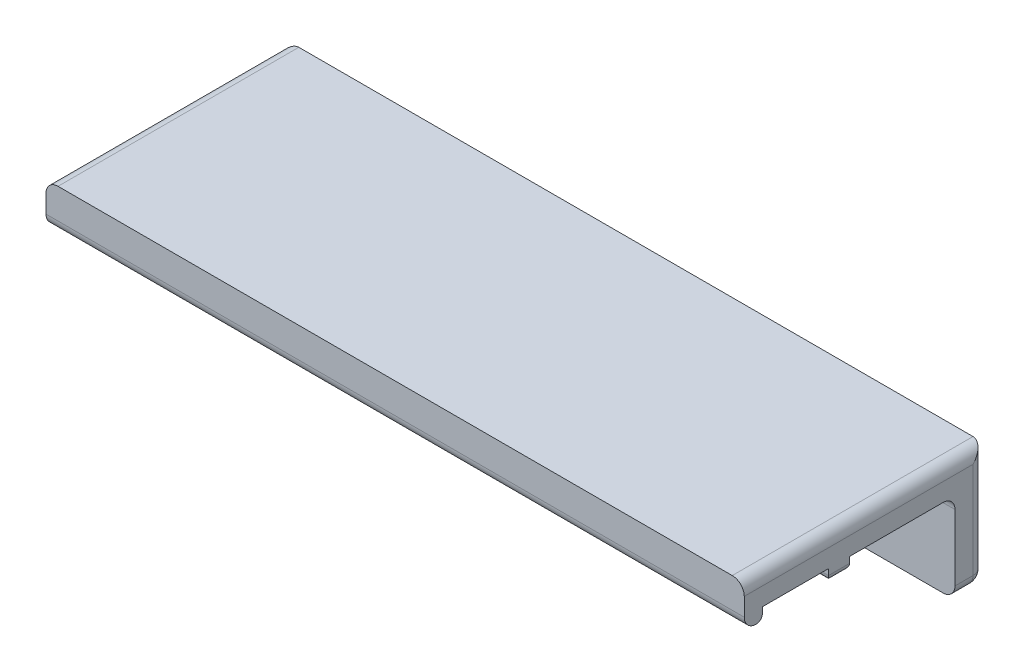
SolidWorks part; units mm, degrees
ref_plane "Front Plane" through (0, 0, 0) normal (0, 0, 1) x (1, 0, 0)
ref_plane "Top Plane" through (0, 0, 0) normal (0, 1, 0) x (1, 0, 0)
ref_plane "Right Plane" through (0, 0, 0) normal (1, 0, 0) x (0, 0, -1)
sketch "Sketch1" plane through (0, 0, 0) normal (0, 0, 1) x (1, 0, 0)
  line L0 (0, 9) -> (116, 9) construction
  line L1 (2, 0) -> (114, 0)
  line L2 (0, 2) -> (0, 20)
  line L3 (0, 20) -> (116, 20)
  line L4 (116, 2) -> (116, 20)
  circle A0 centre (20, 9) radius 2
  circle A1 centre (96, 9) radius 2
  arc A2 (114, 0) -> (116, 2) centre (114, 2) ccw
  arc A3 (2, 0) -> (0, 2) centre (2, 2) cw
  point P13 (116, 0)
  point P16 (0, 0)
  dimension "D3" = 4
  dimension "D4" = 4
  dimension "D5" = 20
  dimension "D6" = 20
  dimension "D7" = 2
  dimension "D1" = 20
  dimension "D2" = 116
  dimension "D8" = 9
extrude "Boss-Extrude1" add sketch "Sketch1" along normal blind 5
sketch "Sketch2" plane through (0, 0, 5) normal (0, 0, 1) x (1, 0, 0)
  line L0 (116, 2) -> (116, 20) construction
  line L1 (0, 20) -> (116, 20)
  line L2 (0, 20) -> (0, 15)
  line L3 (0, 15) -> (116, 15)
  line L4 (116, 20) -> (116, 15)
  dimension "D1" = 5
extrude "Boss-Extrude2" add sketch "Sketch2" along normal blind 35
sketch "Sketch3" plane through (0, 15, 0) normal (0, -1, 0) x (1, 0, 0)
  line L0 (116, 40) -> (116, 5) construction
  line L1 (0, 40) -> (116, 40)
  line L2 (0, 40) -> (0, 37)
  line L3 (0, 37) -> (116, 37)
  line L4 (116, 40) -> (116, 37)
  line L5 (0, 40) -> (0, 5) construction
  line L6 (0, 26) -> (116, 26)
  line L10 (0, 26) -> (0, 22.5)
  line L11 (0, 22.5) -> (116, 22.5)
  line L12 (116, 22.5) -> (116, 26)
  dimension "D1" = 3
  dimension "D2" = 11
extrude "Boss-Extrude3" add sketch "Sketch3" along normal blind 2
fillet "Fillet1" radius 2 8 edges at (0, 11, 0) (0.5858, 0.5858, 0) (58, 0, 0) (115.4142, 0.5858, 0) (58, 13, 40) (0, 20, 20) (116, 11, 0) (116, 20, 20)
fillet "Fillet2" radius 1 5 edges at (58, 13, 26) (116, 13, 24.25) (58, 13, 22.5) (0, 13, 24.25) (58, 13, 37)
fillet "Fillet3" radius 2 1 edges at (58, 15, 5)
